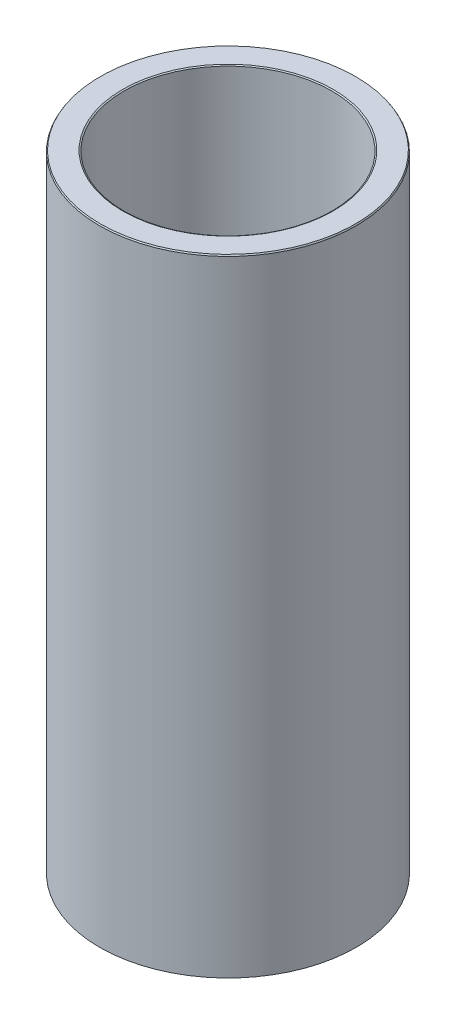
SolidWorks part; units mm, degrees
ref_plane "Front Plane" through (0, 0, 0) normal (0, 0, 1) x (1, 0, 0)
ref_plane "Top Plane" through (0, 0, 0) normal (0, 1, 0) x (1, 0, 0)
ref_plane "Right Plane" through (0, 0, 0) normal (1, 0, 0) x (0, 0, -1)
sketch "Sketch1" plane through (0, 0, 0) normal (0, 1, 0) x (1, 0, 0)
  circle A0 centre (0, 0) radius 52.5
  dimension "SLEEVE_OD" = 105
extrude "Boss-Extrude1" add sketch "Sketch1" along normal blind 256.4033
sketch "Sketch2" plane through (0, 0, 0) normal (0, 1, 0) x (1, 0, 0)
  circle A0 centre (0, 0) radius 42.5415
  dimension "BORE_D" = 85.083
extrude "Cut-Extrude1" cut sketch "Sketch2" along normal through all
chamfer "Chamfer1" distance 0.5284 angle 30 4 edges at (0, 256.4033, 42.5415) (0, 0, 42.5415) (0, 0, 52.5) (0, 256.4033, 52.5) first distance on face at (0, 256.4033, 42.5415) first distance on face at (0, 0, 42.5415) first distance on face at (0, 256.4033, 52.5)
